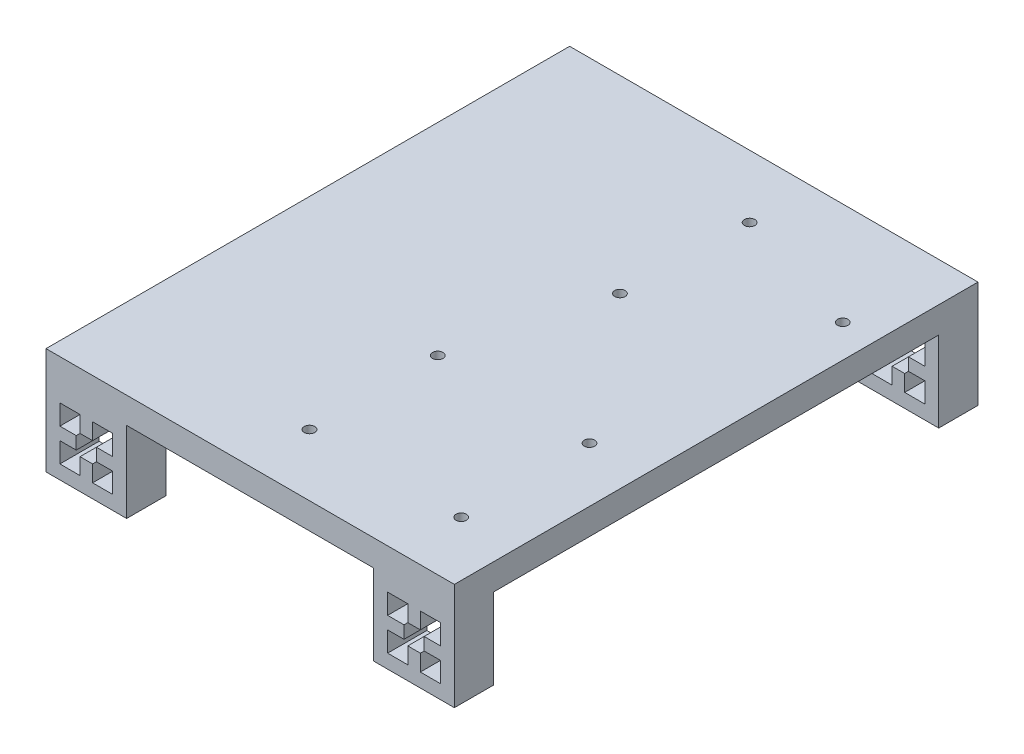
SolidWorks part; units mm, degrees
ref_plane "Plan de face" through (0, 0, 0) normal (0, 0, 1) x (1, 0, 0)
ref_plane "Plan de dessus" through (0, 0, 0) normal (0, 1, 0) x (1, 0, 0)
ref_plane "Plan de droite" through (0, 0, 0) normal (1, 0, 0) x (0, 0, -1)
sketch "Esquisse1" plane through (0, 0, 0) normal (0, 0, 1) x (1, 0, 0)
  line L0 (-30.1176, 6.0342) -> (-30.1176, 10.8342)
  line L1 (-30.1176, 10.8342) -> (-36.3676, 10.8342)
  line L2 (-36.3676, 10.8342) -> (-36.3676, 18.5342)
  line L3 (-36.3676, 18.5342) -> (-28.6676, 18.5342)
  line L4 (-28.6676, 18.5342) -> (-28.6676, 12.2842)
  line L5 (-28.6676, 12.2842) -> (-23.8676, 12.2842)
  line L6 (-23.8676, 18.5342) -> (-23.8676, 12.2842)
  line L7 (-16.1776, 18.5342) -> (-23.8676, 18.5342)
  line L8 (-16.1776, 10.8342) -> (-16.1776, 18.5342)
  line L9 (-22.4276, 10.8342) -> (-16.1776, 10.8342)
  line L10 (-22.4276, 6.0342) -> (-22.4276, 10.8342)
  line L11 (-22.4276, 6.0342) -> (-16.1776, 6.0342)
  line L14 (-30.1176, 6.0342) -> (-36.3676, 6.0342)
  line L15 (-41.6676, 23.8342) -> (-10.8676, 23.8342)
  line L16 (-41.6676, 23.8342) -> (-41.6676, -6.9658)
  line L17 (-10.8676, 23.8342) -> (-10.8676, -6.9658)
  line L29 (-36.3676, 6.0342) -> (-36.3676, -1.6658)
  line L31 (-36.3676, -1.6658) -> (-28.6676, -1.6658)
  line L32 (-28.6676, -1.6658) -> (-28.6676, 4.5842)
  line L34 (-28.6676, 4.5842) -> (-23.8676, 4.5842)
  line L35 (-23.8676, 4.5842) -> (-23.8676, -1.6658)
  line L36 (-23.8676, -1.6658) -> (-16.1776, -1.6658)
  line L37 (-16.1776, -1.6658) -> (-16.1776, 6.0342)
  line L39 (-41.6676, -6.9658) -> (-10.8676, -6.9658)
  dimension "D1" = 30.8
  dimension "D2" = 30.8
  dimension "D3" = 7.7
  dimension "D4" = 6.25
  dimension "D5" = 4.8
extrude "Boss.-Extru.1" add sketch "Esquisse1" along normal blind 15
sketch "Esquisse6" plane through (0, 23.8342, 0) normal (0, 1, 0) x (1, 0, 0)
  line L1 (-41.6676, 185) -> (114.3124, 185)
  line L2 (-41.6676, 185) -> (-41.6676, -15)
  line L3 (-41.6676, -15) -> (114.3124, -15)
  line L4 (114.3124, 185) -> (114.3124, -15)
  line L5 (-41.6676, -15) -> (-41.6676, 0) construction
  line L6 (-10.8676, -15) -> (-41.6676, -15) construction
  dimension "D1" = 155.98
  dimension "D2" = 200
  dimension "D3" = 0
  dimension "D4" = 0
extrude "Boss.-Extru.4" add sketch "Esquisse6" along normal blind 10
sketch "Esquisse16" plane through (0, 0, 15) normal (0, 0, 1) x (1, 0, 0)
  line L0 (95.0624, 6.0342) -> (95.0624, 10.8342)
  line L1 (95.0624, 10.8342) -> (88.8124, 10.8342)
  line L2 (88.8124, 10.8342) -> (88.8124, 18.5342)
  line L3 (88.8124, 18.5342) -> (96.5124, 18.5342)
  line L4 (96.5124, 18.5342) -> (96.5124, 12.2842)
  line L5 (96.5124, 12.2842) -> (101.3124, 12.2842)
  line L6 (101.3124, 18.5342) -> (101.3124, 12.2842)
  line L7 (109.0024, 18.5342) -> (101.3124, 18.5342)
  line L8 (109.0024, 10.8342) -> (109.0024, 18.5342)
  line L9 (102.7524, 10.8342) -> (109.0024, 10.8342)
  line L10 (102.7524, 6.0342) -> (102.7524, 10.8342)
  line L11 (102.7524, 6.0342) -> (109.0024, 6.0342)
  line L14 (95.0624, 6.0342) -> (88.8124, 6.0342)
  line L15 (83.5124, 23.8342) -> (114.3124, 23.8342)
  line L16 (83.5124, 23.8342) -> (83.5124, -6.9658)
  line L17 (114.3124, 23.8342) -> (114.3124, -6.9658)
  line L29 (88.8124, 6.0342) -> (88.8124, -1.6658)
  line L31 (88.8124, -1.6658) -> (96.5124, -1.6658)
  line L32 (96.5124, -1.6658) -> (96.5124, 4.5842)
  line L34 (96.5124, 4.5842) -> (101.3124, 4.5842)
  line L35 (101.3124, 4.5842) -> (101.3124, -1.6658)
  line L36 (101.3124, -1.6658) -> (109.0024, -1.6658)
  line L37 (109.0024, -1.6658) -> (109.0024, 6.0342)
  line L39 (83.5124, -6.9658) -> (114.3124, -6.9658)
  line L41 (-10.8676, 23.8342) -> (114.3124, 23.8342) construction
  line L42 (114.3124, 33.8342) -> (114.3124, 23.8342) construction
  dimension "D1" = 30.8
  dimension "D2" = 30.8
  dimension "D3" = 7.7
  dimension "D4" = 6.25
  dimension "D5" = 4.8
  dimension "D6" = 5.3
  dimension "D7" = 5.3
  dimension "D8" = 0
  dimension "D9" = 0
extrude "Boss.-Extru.12" add sketch "Esquisse16" against normal blind 15
sketch "Esquisse25" plane through (0, 0, -185) normal (0, 0, -1) x (-1, 0, 0)
  line L0 (-102.7624, 6.0342) -> (-102.7624, 10.8342)
  line L1 (-102.7624, 10.8342) -> (-109.0124, 10.8342)
  line L2 (-109.0124, 10.8342) -> (-109.0124, 18.5342)
  line L3 (-109.0124, 18.5342) -> (-101.3124, 18.5342)
  line L4 (-101.3124, 18.5342) -> (-101.3124, 12.2842)
  line L5 (-101.3124, 12.2842) -> (-96.5124, 12.2842)
  line L6 (-96.5124, 18.5342) -> (-96.5124, 12.2842)
  line L7 (-88.8224, 18.5342) -> (-96.5124, 18.5342)
  line L8 (-88.8224, 10.8342) -> (-88.8224, 18.5342)
  line L9 (-95.0724, 10.8342) -> (-88.8224, 10.8342)
  line L10 (-95.0724, 6.0342) -> (-95.0724, 10.8342)
  line L11 (-95.0724, 6.0342) -> (-88.8224, 6.0342)
  line L14 (-102.7624, 6.0342) -> (-109.0124, 6.0342)
  line L15 (-114.3124, 23.8342) -> (-83.5124, 23.8342)
  line L16 (-114.3124, 23.8342) -> (-114.3124, -6.9658)
  line L17 (-83.5124, 23.8342) -> (-83.5124, -6.9658)
  line L29 (-109.0124, 6.0342) -> (-109.0124, -1.6658)
  line L31 (-109.0124, -1.6658) -> (-101.3124, -1.6658)
  line L32 (-101.3124, -1.6658) -> (-101.3124, 4.5842)
  line L34 (-101.3124, 4.5842) -> (-96.5124, 4.5842)
  line L35 (-96.5124, 4.5842) -> (-96.5124, -1.6658)
  line L36 (-96.5124, -1.6658) -> (-88.8224, -1.6658)
  line L37 (-88.8224, -1.6658) -> (-88.8224, 6.0342)
  line L39 (-114.3124, -6.9658) -> (-83.5124, -6.9658)
  line L40 (-114.3124, 23.8342) -> (41.6676, 23.8342) construction
  line L41 (-114.3124, 33.8342) -> (-114.3124, 23.8342) construction
  dimension "D1" = 30.8
  dimension "D2" = 30.8
  dimension "D3" = 7.7
  dimension "D4" = 6.25
  dimension "D5" = 4.8
  dimension "D6" = 5.3
  dimension "D7" = 5.3
  dimension "D8" = 0
  dimension "D9" = 0
extrude "Boss.-Extru.21" add sketch "Esquisse25" against normal blind 15
sketch "Esquisse26" plane through (0, 0, -185) normal (0, 0, -1) x (-1, 0, 0)
  line L0 (22.4176, 6.0342) -> (22.4176, 10.8342)
  line L1 (22.4176, 10.8342) -> (16.1676, 10.8342)
  line L2 (16.1676, 10.8342) -> (16.1676, 18.5342)
  line L3 (16.1676, 18.5342) -> (23.8676, 18.5342)
  line L4 (23.8676, 18.5342) -> (23.8676, 12.2842)
  line L5 (23.8676, 12.2842) -> (28.6676, 12.2842)
  line L6 (28.6676, 18.5342) -> (28.6676, 12.2842)
  line L7 (36.3576, 18.5342) -> (28.6676, 18.5342)
  line L8 (36.3576, 10.8342) -> (36.3576, 18.5342)
  line L9 (30.1076, 10.8342) -> (36.3576, 10.8342)
  line L10 (30.1076, 6.0342) -> (30.1076, 10.8342)
  line L11 (30.1076, 6.0342) -> (36.3576, 6.0342)
  line L14 (22.4176, 6.0342) -> (16.1676, 6.0342)
  line L15 (10.8676, 23.8342) -> (41.6676, 23.8342)
  line L16 (10.8676, 23.8342) -> (10.8676, -6.9658)
  line L17 (41.6676, 23.8342) -> (41.6676, -6.9658)
  line L29 (16.1676, 6.0342) -> (16.1676, -1.6658)
  line L31 (16.1676, -1.6658) -> (23.8676, -1.6658)
  line L32 (23.8676, -1.6658) -> (23.8676, 4.5842)
  line L34 (23.8676, 4.5842) -> (28.6676, 4.5842)
  line L35 (28.6676, 4.5842) -> (28.6676, -1.6658)
  line L36 (28.6676, -1.6658) -> (36.3576, -1.6658)
  line L37 (36.3576, -1.6658) -> (36.3576, 6.0342)
  line L39 (10.8676, -6.9658) -> (41.6676, -6.9658)
  line L40 (10.8676, 23.8342) -> (41.6676, 23.8342) construction
  line L41 (41.6676, 33.8342) -> (41.6676, 23.8342) construction
  dimension "D1" = 30.8
  dimension "D2" = 30.8
  dimension "D3" = 7.7
  dimension "D4" = 6.25
  dimension "D5" = 4.8
  dimension "D6" = 5.3
  dimension "D7" = 5.3
  dimension "D8" = 0
  dimension "D9" = 0
extrude "Boss.-Extru.22" add sketch "Esquisse26" against normal blind 15
sketch "Esquisse27" plane through (0, 33.8342, 0) normal (0, 1, 0) x (1, 0, 0)
  circle A0 centre (101.7947, 145.8495) radius 2
  point P2 (89.437, 143.3943)
  point P3 (91.9806, 144.8905)
  point P4 (94.225, 145.115)
  point P5 (97.1702, 149.55)
  point P6 (0, 0)
  point P7 (101.5217, 143.8231)
  point P8 (101.1496, 145.4194)
  point P9 (101.7947, 145.8495)
  point P10 (0, 0)
  point P11 (0, 0)
  point P12 (0, 0)
extrude "Enlèv. mat.-Extru.1" cut sketch "Esquisse27" against normal blind 10
sketch "Esquisse28" plane through (0, 33.8342, 0) normal (0, 1, 0) x (1, 0, 0)
  circle A0 centre (50.9947, 161.0895) radius 2
extrude "Enlèv. mat.-Extru.2" cut sketch "Esquisse28" against normal blind 10
sketch "Esquisse29" plane through (0, 33.8342, 0) normal (0, 1, 0) x (1, 0, 0)
  circle A0 centre (49.7247, 112.8295) radius 2
extrude "Enlèv. mat.-Extru.3" cut sketch "Esquisse29" against normal blind 10
chamfer "Chanfrein1" distance 3 angle 45 1 edges at (47.7247, 23.8342, -112.8295)
chamfer "Chanfrein2" distance 3 angle 45 1 edges at (48.9947, 23.8342, -161.0895)
chamfer "Chanfrein3" distance 3 angle 45 1 edges at (99.7947, 23.8342, -145.8495)
sketch "Esquisse30" plane through (0, 33.8342, 0) normal (0, 1, 0) x (1, 0, 0)
  circle A0 centre (93.4091, 8.5018) radius 2
  circle A1 centre (93.4091, 57.5018) radius 2
  circle A2 centre (35.4091, 57.5612) radius 2
  circle A3 centre (35.4091, 8.5612) radius 2
  point P8 (93.4091, 8.5452)
  point P9 (51.051, 42.8569)
  point P10 (93.4091, 42.8569)
  point P11 (51.051, 8.5452)
  point P12 (0, 0)
  point P13 (0, 0)
  point P14 (93.4091, 8.5612)
  point P15 (35.4091, 57.5452)
extrude "Enlèv. mat.-Extru.4" cut sketch "Esquisse30" against normal blind 10
chamfer "Chanfrein4" distance 3 angle 45 4 edges at (91.4091, 23.8342, -57.5018) (91.4091, 23.8342, -8.5018) (33.4091, 23.8342, -8.5612) (33.4091, 23.8342, -57.5612)
